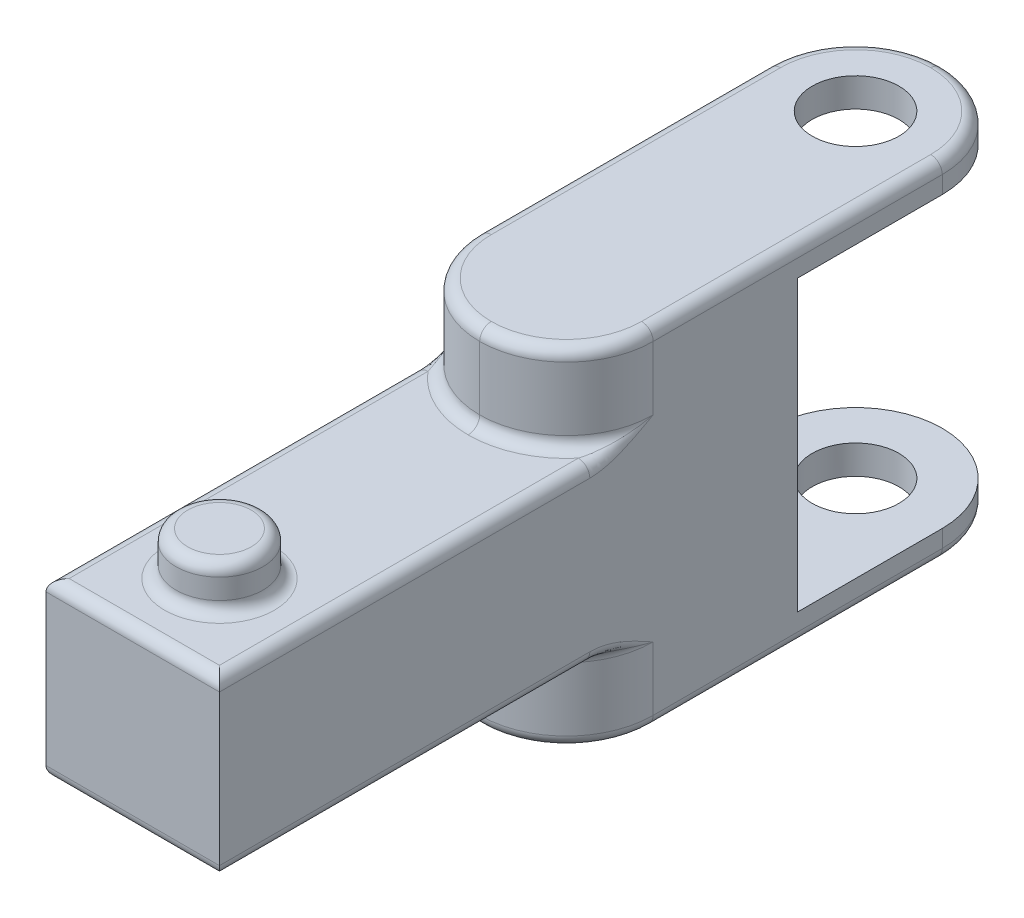
SolidWorks part; units mm, degrees
ref_plane "Front Plane" through (0, 0, 0) normal (0, 0, 1) x (1, 0, 0)
ref_plane "Top Plane" through (0, 0, 0) normal (0, 1, 0) x (1, 0, 0)
ref_plane "Right Plane" through (0, 0, 0) normal (1, 0, 0) x (0, 0, -1)
sketch "Sketch2" plane through (0, 0, 0) normal (0, 0, 1) x (1, 0, 0)
  line L1 (15, 15) -> (-15, 15)
  line L2 (15, 15) -> (15, -15)
  line L3 (15, -15) -> (-15, -15)
  line L4 (-15, 15) -> (-15, -15)
  line L5 (15, 15) -> (-15, -15) construction
  line L6 (15, -15) -> (-15, 15) construction
  point P0 (0, 0)
  dimension "D1" = 30
  dimension "D2" = 30
extrude "Boss-Extrude1" add sketch "Sketch2" along normal blind 100
sketch "Sketch3" plane through (0, 0, 0) normal (0, 0, -1) x (-1, 0, 0)
  line L0 (-15, 15) -> (15, 15) construction
  line L1 (15, 30) -> (-15, 30)
  line L2 (15, 30) -> (15, -30)
  line L3 (15, -30) -> (-15, -30)
  line L4 (-15, 30) -> (-15, -30)
  line L5 (15, 30) -> (-15, -30) construction
  line L6 (15, -30) -> (-15, 30) construction
  point P0 (0, 0)
  line M6 (15, 15) -> (-15, 15)
  line M8 (-15, -15) -> (15, -15)
  dimension "D1" = 60
extrude "Boss-Extrude2" add sketch "Sketch3" along normal mid plane 80 contours L1 L4 L2 M6 | L4 L3 L2 M8 region at (0, 22.5, 0) region at (0, -22.5, 0)
fillet "Fillet1" radius 15 8 edges at (15, -22.5, 40) (-15, -22.5, 40) (15, 22.5, 40) (-15, 22.5, 40) (15, -22.5, -40) (15, 22.5, -40) (-15, -22.5, -40) (-15, 22.5, -40)
sketch "Sketch5" plane through (0, -30, 0) normal (0, -1, 0) x (1, 0, 0)
  line L0 (0, -40) -> (0, 0) construction
  line L1 (0, 0) -> (15, 0) construction
  line L2 (15, -25) -> (15, 25) construction
  line L3 (-15, -25) -> (15, -25) construction
  circle A1 centre (0, -25) radius 7.5
  dimension "D1" = 15
extrude "Cut-Extrude1" cut sketch "Sketch5" against normal blind 80
ref_plane "Plane1" through (0, 0, 0) normal (0, -1, 0) x (-1, 0, 0)
sketch "Sketch6" plane through (0, 0, 0) normal (0, 1, 0) x (1, 0, 0)
  line L0 (0, -100) -> (0, -85) construction
  line L2 (15, -100) -> (-15, -100) construction
  circle A0 centre (0, -85) radius 7.5
  dimension "D2" = 15
  dimension "D1" = 15
extrude "Boss-Extrude3" add sketch "Sketch6" along normal mid plane 45
fillet "Fillet2" radius 2 26 edges at (10.6066, -30, 35.6066) (15, -30, 0) (10.6066, -30, -35.6066) (-10.6066, -30, -35.6066) (-15, -30, 0) (-15, 30, 0) (-10.6066, 30, -35.6066) (10.6066, 30, -35.6066) (15, 30, 0) (10.6066, 30, 35.6066) (10.6066, -15, 35.6066) (10.6066, 15, 35.6066) (-10.6066, -30, 35.6066) (-10.6066, 30, 35.6066) (15, -15, 62.5) (0, -15, 100) (-15, -15, 62.5) (-10.6066, -15, 35.6066) (0, 15, 100) (15, 15, 62.5) (-15, 15, 62.5) (-10.6066, 15, 35.6066) (7.5, 15, 85) (-7.5, -15, 85) (0, -22.5, 92.5) (0, 22.5, 92.5)
sketch "Sketch8" plane through (-15, 0, 0) normal (-1, 0, 0) x (0, 0, 1)
  line L0 (0, -25) -> (0, 25) construction
  line L1 (0, 25) -> (0, -25)
  line L2 (0, -25) -> (-51.4468, -25)
  line L3 (-51.4468, -25) -> (-51.4468, 25)
  line L4 (-51.4468, 25) -> (0, 25)
  point P4 (0, 0)
  dimension "D1" = 50
extrude "Cut-Extrude2" cut sketch "Sketch8" against normal through all
